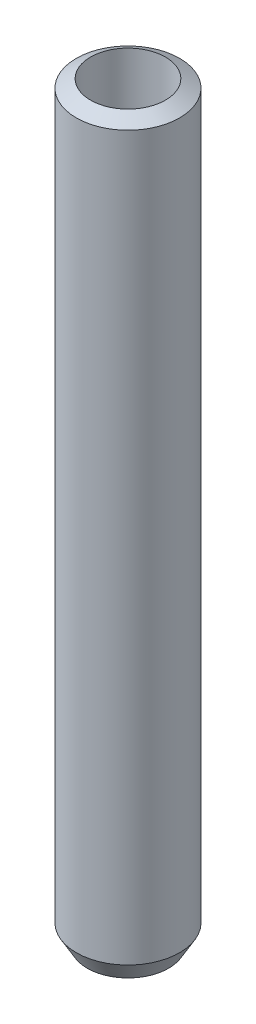
SolidWorks part; units mm, degrees
ref_plane "Front Plane" through (0, 0, 0) normal (0, 0, 1) x (1, 0, 0)
ref_plane "Top Plane" through (0, 0, 0) normal (0, 1, 0) x (1, 0, 0)
ref_plane "Right Plane" through (0, 0, 0) normal (1, 0, 0) x (0, 0, -1)
sketch "Sketch1" plane through (0, 0, 0) normal (0, 1, 0) x (1, 0, 0)
  circle A0 centre (0, 0) radius 20
  dimension "SHAFT_OD" = 40
extrude "Boss-Extrude1" add sketch "Sketch1" along normal blind 291.5617
sketch "Sketch2" plane through (0, 0, 0) normal (0, 1, 0) x (1, 0, 0)
  circle A0 centre (0, 0) radius 14.4875
  dimension "BORE_D" = 28.9749
extrude "Cut-Extrude1" cut sketch "Sketch2" along normal through all
chamfer "Chamfer1" distance 4.2368 angle 60 2 edges at (0, 291.5617, 20) (0, 0, 20) first distance on face at (0, 291.5617, 20) first distance on face at (0, 0, 14.4875)
